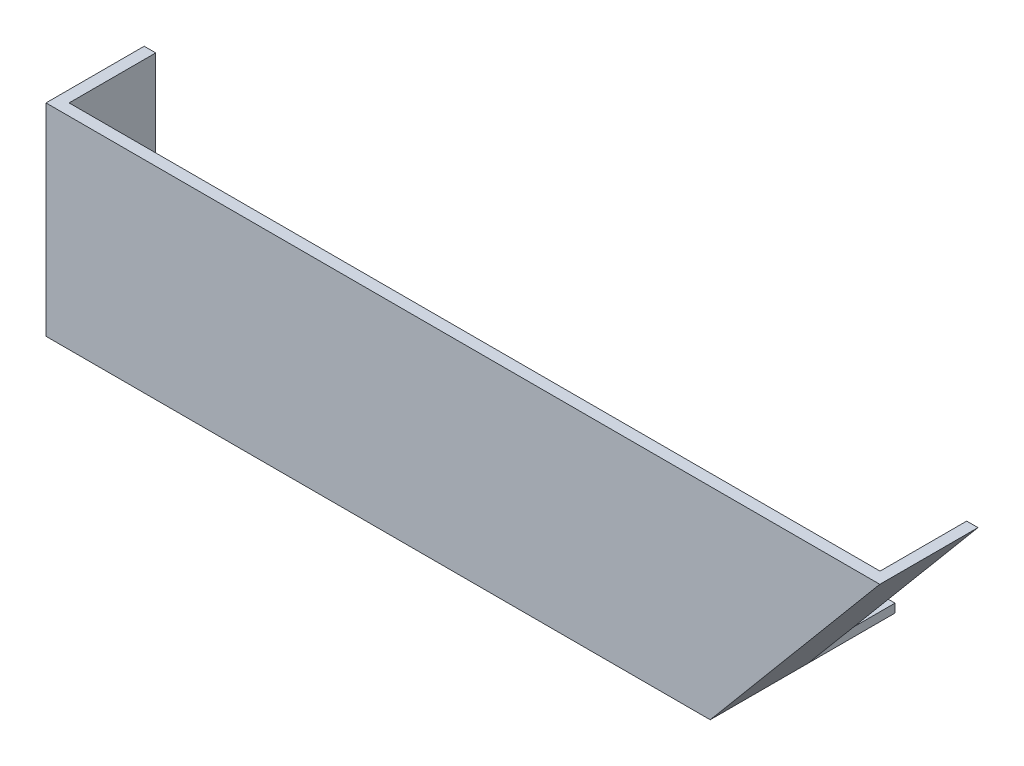
SolidWorks part; units mm, degrees
ref_plane "Front Plane" through (0, 0, 0) normal (0, 0, 1) x (1, 0, 0)
ref_plane "Top Plane" through (0, 0, 0) normal (0, 1, 0) x (1, 0, 0)
ref_plane "Right Plane" through (0, 0, 0) normal (1, 0, 0) x (0, 0, -1)
sketch "Sketch1" plane through (0, 0, 0) normal (0, 0, 1) x (1, 0, 0)
  line L0 (95.0342, 49.4349) -> (153.7712, 119.4349)
  line L1 (-134.9658, 119.4349) -> (95.0342, 119.4349)
  line L2 (-134.9658, 119.4349) -> (-134.9658, 49.4349)
  line L3 (-134.9658, 49.4349) -> (95.0342, 49.4349)
  line L5 (-134.9658, 119.4349) -> (95.0342, 49.4349) construction
  line L6 (-134.9658, 49.4349) -> (95.0342, 119.4349) construction
  line L7 (153.7712, 119.4349) -> (95.0342, 119.4349)
  point P0 (-19.9658, 84.4349)
  dimension "D1" = 70
  dimension "D2" = 230
  dimension "D3" = 50
extrude "Boss-Extrude1" add sketch "Sketch1" along normal blind 4
sketch "Sketch2" plane through (0, 0, 0) normal (0, 0, -1) x (-1, 0, 0)
  line L0 (134.9658, 49.4349) -> (-95.0342, 49.4349) construction
  line L1 (134.9658, 119.4349) -> (130.9658, 119.4349)
  line L2 (134.9658, 119.4349) -> (134.9658, 49.4349)
  line L3 (134.9658, 49.4349) -> (130.9658, 49.4349)
  line L4 (130.9658, 119.4349) -> (130.9658, 49.4349)
  dimension "D1" = 4
extrude "Boss-Extrude2" add sketch "Sketch2" along normal blind 30
sketch "Sketch3" plane through (0, 0, 0) normal (0, 0, -1) x (-1, 0, 0)
  line L0 (130.9658, 119.4349) -> (130.9658, 49.4349) construction
  line L1 (-95.0342, 49.4349) -> (130.9658, 49.4349)
  line L2 (-95.0342, 49.4349) -> (-95.0342, 52.4349)
  line L3 (-95.0342, 52.4349) -> (130.9658, 52.4349)
  line L4 (130.9658, 49.4349) -> (130.9658, 52.4349)
  dimension "D1" = 3
extrude "Boss-Extrude3" add sketch "Sketch3" along normal blind 60
sketch "Sketch4" plane through (0, 0, 0) normal (0, 0, -1) x (-1, 0, 0)
  line L0 (-153.7712, 119.4349) -> (-95.0342, 49.4349)
  line L1 (-95.0342, 49.4349) -> (-92.7361, 51.3633)
  line L2 (-92.7361, 51.3633) -> (-149.855, 119.4349)
  line L3 (-149.855, 119.4349) -> (-153.7712, 119.4349)
  line L4 (-153.7712, 119.4349) -> (130.9658, 119.4349) construction
  dimension "D1" = 3
extrude "Boss-Extrude4" add sketch "Sketch4" along normal blind 30
